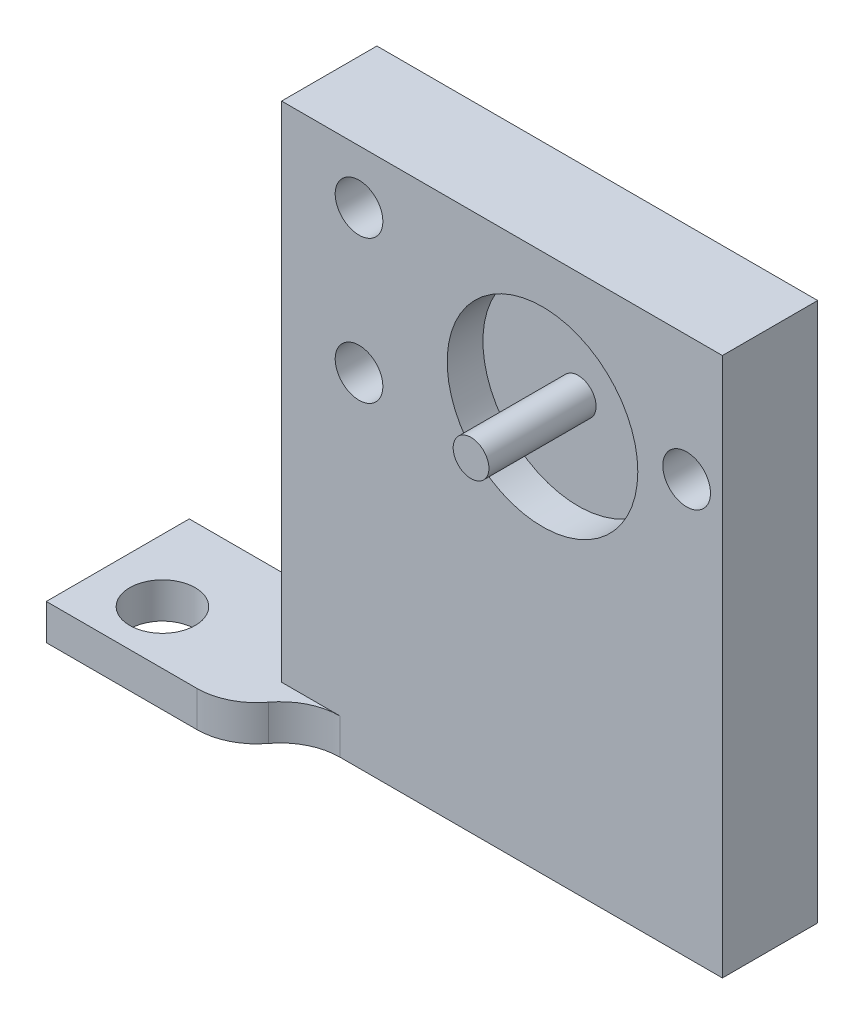
SolidWorks part; units mm, degrees
ref_plane "Plan de face" through (0, 0, 0) normal (0, 0, 1) x (1, 0, 0)
ref_plane "Plan de dessus" through (0, 0, 0) normal (0, 1, 0) x (1, 0, 0)
ref_plane "Plan de droite" through (0, 0, 0) normal (1, 0, 0) x (0, 0, -1)
sketch "Esquisse1" plane through (0, 0, 0) normal (0, 0, 1) x (1, 0, 0)
  line L0 (-2.5, 15.125) -> (9.3, -8.875) construction
  line L1 (18.5, -21.125) -> (-18.5, -21.125)
  line L2 (18.5, -21.125) -> (18.5, 21.125)
  line L3 (18.5, 21.125) -> (-18.5, 21.125)
  line L4 (-18.5, -21.125) -> (-18.5, 21.125)
  line L5 (18.5, -21.125) -> (-18.5, 21.125) construction
  line L6 (18.5, 21.125) -> (-18.5, -21.125) construction
  line L7 (-2.5, 15.125) -> (9.3, 15.125) construction
  line L8 (-2.5, 15.125) -> (-2.5, -8.875) construction
  line L9 (-2.5, -8.875) -> (9.3, -8.875) construction
  line L10 (9.3, 15.125) -> (9.3, -8.875) construction
  circle A0 centre (3.4, 9.125) radius 6
  point P0 (0, 0)
  point P10 (6.876, 11.046)
  point P13 (5.6683, 5.6249)
  point P14 (5.3565, 6)
  point P15 (5.1313, 6)
  point P16 (1.9794, 6)
  point P17 (5.4, 5.0338)
  point P18 (0, 0)
  point P19 (3.4, 3.3872)
  point P20 (5.7567, 10.625)
  point P21 (2.444, 10.6372)
  point P22 (2.45, 10.625)
  point P23 (5.5852, 10.625)
  point P24 (-3.6826, 10.625)
  point P25 (3.4, 3.125)
  point P26 (0, 0)
  point P27 (5.4, 10.625)
  point P28 (11.3, -7.375)
  point P29 (11.3, 16.625)
  dimension "D6" = 12
  dimension "D1" = 37
  dimension "D2" = 36.25
  dimension "D3" = 11.8
  dimension "D4" = 24
  dimension "D5" = 16
  dimension "D7" = 6
extrude "Boss.-Extru.1" add sketch "Esquisse1" along normal blind 12 contours A0 | L4 L1 L2 L3 A0 region at (-0.2652, -0.7117, 0) region at (3.4, 9.125, 0)
sketch "Esquisse2" plane through (0, 0, 12) normal (0, 0, 1) x (1, 0, 0)
  line L4 (-18.5, -21.125) -> (18.5, -21.125)
  line L5 (-18.5, 21.125) -> (-18.5, -21.125)
  line L6 (18.5, 21.125) -> (-18.5, 21.125)
  line L7 (18.5, -21.125) -> (18.5, 21.125)
  line L8 (-18.5, -21.125) -> (18.5, -21.125) construction
  line L9 (-18.5, 21.125) -> (-18.5, -21.125) construction
  line L10 (18.5, 21.125) -> (-18.5, 21.125) construction
  line L11 (18.5, -21.125) -> (18.5, 21.125) construction
  circle A0 centre (3.4, 9.125) radius 1.5
  circle A1 centre (3.4, 9.125) radius 6
  circle A2 centre (3.4, 9.125) radius 6
  dimension "D3" = 3
  dimension "D1" = 0
  dimension "D2" = 0
extrude "Enlèv. mat.-Extru.1" cut sketch "Esquisse2" against normal offset from surface (3 mm away) 3 up to face at (0, 0, 12)
sketch "Esquisse3" plane through (0, -21.125, 0) normal (0, -1, 0) x (1, 0, 0)
  line L0 (18.5, 0) -> (-18.5, 0) construction
  line L1 (-18.5, 12) -> (-34.25, 12)
  line L2 (-18.5, 12) -> (-18.5, 0)
  line L3 (-18.5, 0) -> (-34.25, 0)
  line L4 (-34.25, 12) -> (-34.25, 0)
  line L9 (-18.5, 0) -> (18.5, 0)
  line L10 (18.5, 0) -> (18.5, 12)
  line L11 (18.5, 12) -> (-18.5, 12)
  line L12 (-18.5, 12) -> (-18.5, 0)
  line L13 (-18.5, 0) -> (18.5, 0)
  line L14 (18.5, 0) -> (18.5, 12)
  line L15 (18.5, 12) -> (-18.5, 12)
  line L16 (-18.5, 12) -> (-18.5, 0)
  circle A0 centre (-29, 7.5) radius 2.75
  point P7 (0, 0)
  point P9 (-34.4458, -1.4376)
  line M6 (-18.5, 0) -> (18.5, 0)
  line M7 (18.5, 0) -> (18.5, 12)
  line M8 (18.5, 12) -> (-18.5, 12)
  line M9 (-18.5, 12) -> (-18.5, 0)
  dimension "D2" = 5.5
  dimension "D1" = 10.5
  dimension "D3" = 5.25
  dimension "D5" = 7.5
  dimension "D4" = 0
extrude "Boss.-Extru.2" add sketch "Esquisse3" along normal blind 3 contours M9 M6 M7 M8 | L1 L4 L3 A0 M9 region at (-25.9976, -21.125, 5.7843) region at (0, -21.125, 6)
sketch "Esquisse4" plane through (0, 0, 12) normal (0, 0, 1) x (1, 0, 0)
  line L1 (-18.5, 21.125) -> (18.5, 21.125)
  line L2 (-18.5, 21.125) -> (-18.5, -24.125)
  line L3 (-18.5, -24.125) -> (18.5, -24.125)
  line L4 (18.5, 21.125) -> (18.5, -24.125)
  circle A0 centre (3.4, 9.125) radius 8
  circle A2 centre (3.4, 9.125) radius 1.5 construction
  circle A3 centre (3.4, 9.125) radius 1.5
  circle A4 centre (3.4, 9.125) radius 6 construction
  circle A5 centre (3.4, 9.125) radius 6 construction
  circle M1 centre (3.4, 9.125) radius 6
  line M2 (-18.5, 21.125) -> (-18.5, -21.125)
  line M5 (-34.25, -24.125) -> (18.5, -24.125)
  line M6 (18.5, -24.125) -> (18.5, 21.125)
  line M7 (18.5, 21.125) -> (-18.5, 21.125)
  dimension "D1" = 2
extrude "Enlèv. mat.-Extru.2" cut sketch "Esquisse4" against normal blind 4 contours L2 M2 M5 M6 M7 M1 region at (-0.464, -2.9501, 12)
extrude "Enlèv. mat.-Extru.4" cut sketch "Esquisse4<3>" against normal offset from surface (7 mm away) 3 contours A3 M1 | A0 M1 region at (-4.3737, 9.125, 12) region at (-2.4303, 9.125, 12) up to face at (11.4, 9.125, 8) offset beyond the face yes
sketch "Esquisse4<3>" plane through (0, 0, 12) normal (0, 0, 1) x (1, 0, 0) same geometry as "Esquisse4"
fillet "Congé2" radius 5 1 edges at (-18.5, -22.625, 8)
fillet "Congé3" radius 5 1 edges at (-18.5, -22.625, 12)
sketch "Esquisse5" plane through (0, 0, 8) normal (0, 0, 1) x (1, 0, 0)
  line L0 (-12, 16.625) -> (-12, 4.625) construction
  line L1 (18.5, 21.125) -> (-18.5, 21.125) construction
  line L2 (-18.5, 21.125) -> (-18.5, -21.125) construction
  circle A0 centre (-12, 16.625) radius 2
  circle A1 centre (-12, 4.625) radius 2
  circle A2 centre (15.5, 10.625) radius 2
  point P6 (-12, 10.625)
  dimension "D1" = 4
  dimension "D2" = 4.5
  dimension "D3" = 6.5
  dimension "D4" = 12
  dimension "D5" = 27.5
extrude "Enlèv. mat.-Extru.5" cut sketch "Esquisse5" against normal through all
extrude "Boss.-Extru.3" add sketch "Esquisse2<2>" along normal blind 2 contours A0 region at (3.4, 9.125, 12)
sketch "Esquisse2<2>" plane through (0, 0, 12) normal (0, 0, 1) x (1, 0, 0) same geometry as "Esquisse2"
